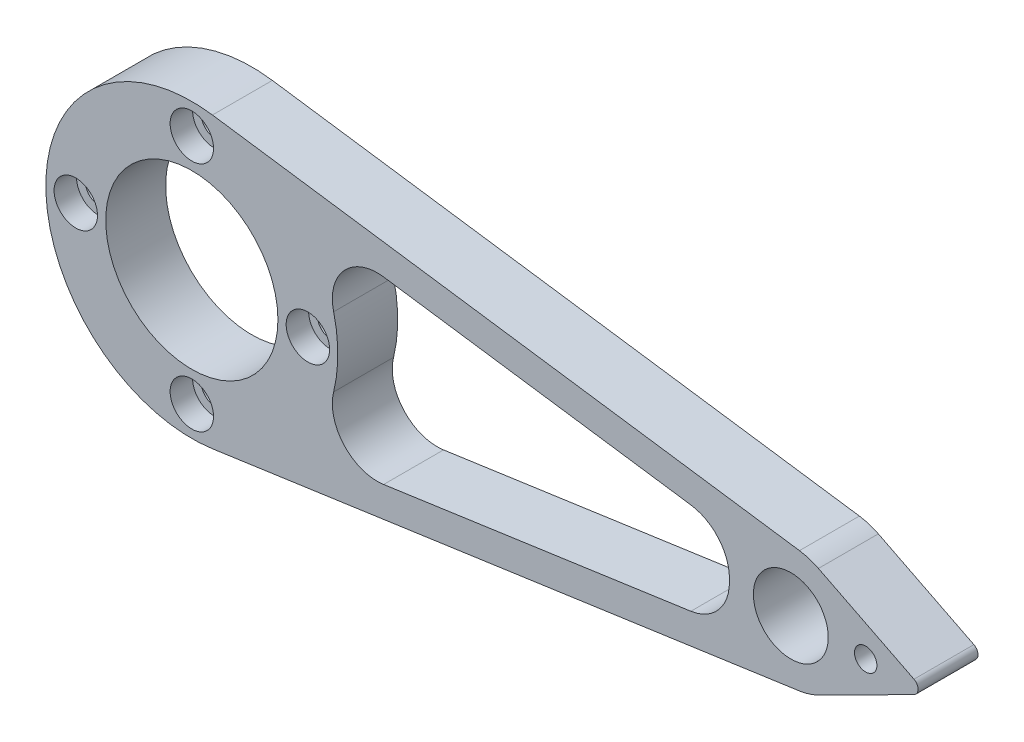
SolidWorks part; units mm, degrees
ref_plane "Plan de face" through (0, 0, 0) normal (0, 0, 1) x (1, 0, 0)
ref_plane "Plan de dessus" through (0, 0, 0) normal (0, 1, 0) x (1, 0, 0)
ref_plane "Plan de droite" through (0, 0, 0) normal (1, 0, 0) x (0, 0, -1)
sketch "Esquisse1" plane through (0, 0, 0) normal (0, 0, 1) x (1, 0, 0)
  circle A0 centre (0, 0) radius 15.5 construction
  circle A1 centre (0, 15.5) radius 1.7
  circle A2 centre (15.5, 0) radius 1.7
  circle A3 centre (0, -15.5) radius 1.7
  circle A4 centre (-15.5, 0) radius 1.7
  circle A5 centre (0, 0) radius 11.5
  circle A6 centre (0, 0) radius 19.5
  point P14 (0, 0)
  dimension "D1" = 31
  dimension "D2" = 3.4
  dimension "D4" = 4
  dimension "D5" = 4
  dimension "D3" = 4
extrude "Boss.-Extru.1" add sketch "Esquisse1" along normal blind 8
sketch "Esquisse2" plane through (0, 0, 8) normal (0, 0, 1) x (1, 0, 0)
  line L0 (0, 0) -> (80, 0) construction
  line L1 (2.7544, 19.3045) -> (81.1582, 8.1178)
  line L2 (2.7544, -19.3045) -> (81.1582, -8.1178)
  circle A0 centre (80, 0) radius 5
  arc A1 (81.1582, -8.1178) -> (81.1582, 8.1178) centre (80, 0) ccw
  circle A2 centre (0, 0) radius 19.5 construction
  arc A3 (2.7544, -19.3045) -> (2.7544, 19.3045) centre (0, 0) ccw
  dimension "D1" = 10
  dimension "D2" = 3.2
  dimension "D3" = 80
extrude "Boss.-Extru.2" add sketch "Esquisse2" against normal blind 8
sketch "Esquisse3" plane through (0, 0, 8) normal (0, 0, 1) x (1, 0, 0)
  line L0 (13.9029, 13.6733) -> (73.6211, 5.1527)
  line L1 (81.1582, 8.1178) -> (2.7544, 19.3045) construction
  line L2 (0, 0) -> (80, 0) construction
  line L3 (13.9029, -13.6733) -> (73.6211, -5.1527)
  arc A0 (13.9029, -13.6733) -> (13.9029, 13.6733) centre (0, 0) ccw
  arc A1 (73.6211, 5.1527) -> (73.6211, -5.1527) centre (80, 0) ccw
  dimension "D1" = 4
extrude "Enlèv. mat.-Extru.1" cut sketch "Esquisse3" against normal through all
fillet "Congé1" radius 6 4 edges at (73.6211, -5.1527, 4) (73.6211, 5.1527, 4) (13.9029, -13.6733, 4) (13.9029, 13.6733, 4)
sketch "Esquisse4" plane through (0, 0, 8) normal (0, 0, 1) x (1, 0, 0)
  line L0 (80, 0) -> (96, 0) construction
  line L1 (83.69, 7.3228) -> (96.45, 0.893)
  line L2 (83.69, -7.3228) -> (96.45, -0.893)
  arc A0 (81.1582, -8.1178) -> (81.1582, 8.1178) centre (80, 0) ccw construction
  arc A1 (83.69, -7.3228) -> (83.69, 7.3228) centre (80, 0) ccw
  arc A2 (96.45, -0.893) -> (96.45, 0.893) centre (96, 0) ccw
  circle A3 centre (90, 0) radius 1.5
  dimension "D1" = 2
  dimension "D3" = 3
  dimension "D2" = 16
  dimension "D4" = 10
extrude "Boss.-Extru.3" add sketch "Esquisse4" against normal blind 8
sketch "Esquisse5" plane through (0, 0, 8) normal (0, 0, 1) x (1, 0, 0)
  circle A0 centre (0, 15.5) radius 2.9
  circle A1 centre (15.5, 0) radius 2.9
  circle A2 centre (0, -15.5) radius 2.9
  circle A3 centre (-15.5, 0) radius 2.9
  dimension "D1" = 5.8
extrude "Enlèv. mat.-Extru.2" cut sketch "Esquisse5" against normal blind 3
